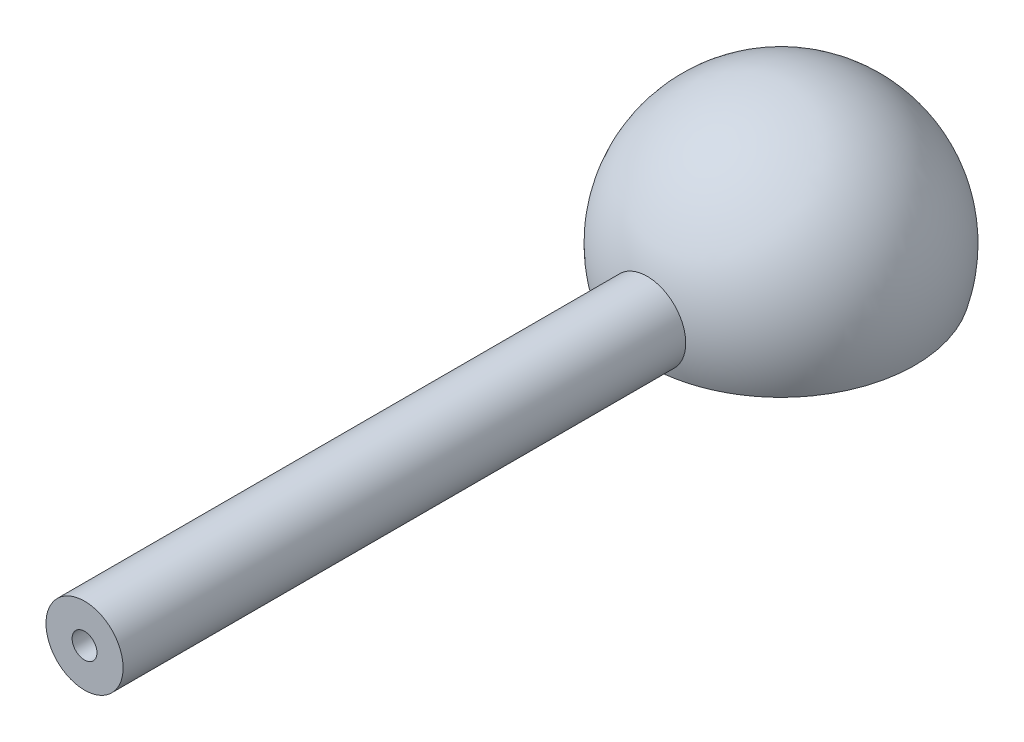
SolidWorks part; units mm, degrees
ref_plane "Alzado" through (0, 0, 0) normal (0, 0, 1) x (1, 0, 0)
ref_plane "Planta" through (0, 0, 0) normal (0, 1, 0) x (1, 0, 0)
ref_plane "Vista lateral" through (0, 0, 0) normal (1, 0, 0) x (0, 0, -1)
sketch "Croquis2" plane through (0, 0, 0) normal (0, 0, 1) x (1, 0, 0)
  circle A0 centre (0, 0) radius 9
  dimension "D1" = 18
extrude "Saliente-Extruir1" add sketch "Croquis2" along normal blind 130
sketch "Croquis4" plane through (0, 0, 130) normal (0, 0, 1) x (1, 0, 0)
  circle A0 centre (0, 0) radius 2.9
  dimension "D1" = 5.8
extrude "Cortar-Extruir1" cut sketch "Croquis4" against normal blind 110
sketch "Croquis5" plane through (0, 0, 0) normal (0, 1, 0) x (1, 0, 0)
  line L0 (-9, 0) -> (-9, 1.271)
  line L2 (-9, 0) -> (0, 0)
  line L3 (0, 65) -> (0, 0)
  ellipse E0 centre (0, 32.5) end of major axis (0, 0) minor radius 32.5 (0, 65) -> (-9, 1.271) ccw
  dimension "D1" = 65
  dimension "D2" = 65
revolve "Revolución1" add sketch "Croquis5" angle 360 about L3
sketch "Croquis6" plane through (0, 0, 0) normal (0, 1, 0) x (1, 0, 0)
  line L0 (0.379, 60.2609) -> (0.379, 5.2609)
  arc A0 (0.379, 60.2609) -> (0.379, 5.2609) centre (0.379, 32.7609) ccw
  point P1 (0.379, 32.7609)
  dimension "D1" = 55
revolve "Cortar-Revolución7" cut sketch "Croquis6" angle 360 about L0
sketch "Croquis8" plane through (0, 0, 0) normal (0, 1, 0) x (1, 0, 0)
  circle A0 centre (0, 32.6202) radius 30
  point P2 (0, 32.6202)
  dimension "D1" = 60
extrude "Cortar-Extruir4" cut sketch "Croquis8" against normal blind 50
sketch "Croquis9" plane through (0, 0, 0) normal (1, 0, 0) x (0, 0, -1)
  line L0 (-130, -9) -> (1.271, -9) construction
  line L1 (-0.2352, -25.0459) -> (68.5338, -25.0459)
  line L2 (-0.2352, -25.0459) -> (-0.2352, -9)
  line L3 (-0.2352, -9) -> (68.5338, -9)
  line L4 (68.5338, -25.0459) -> (68.5338, -9)
  line L5 (-0.2352, -25.0459) -> (68.5338, -9) construction
  line L6 (-0.2352, -9) -> (68.5338, -25.0459) construction
  point P0 (34.1493, -17.0229)
extrude "Cortar-Extruir5" cut sketch "Croquis9" against normal blind 50 and the other way blind 50 contours L2 L3 L4 L1
